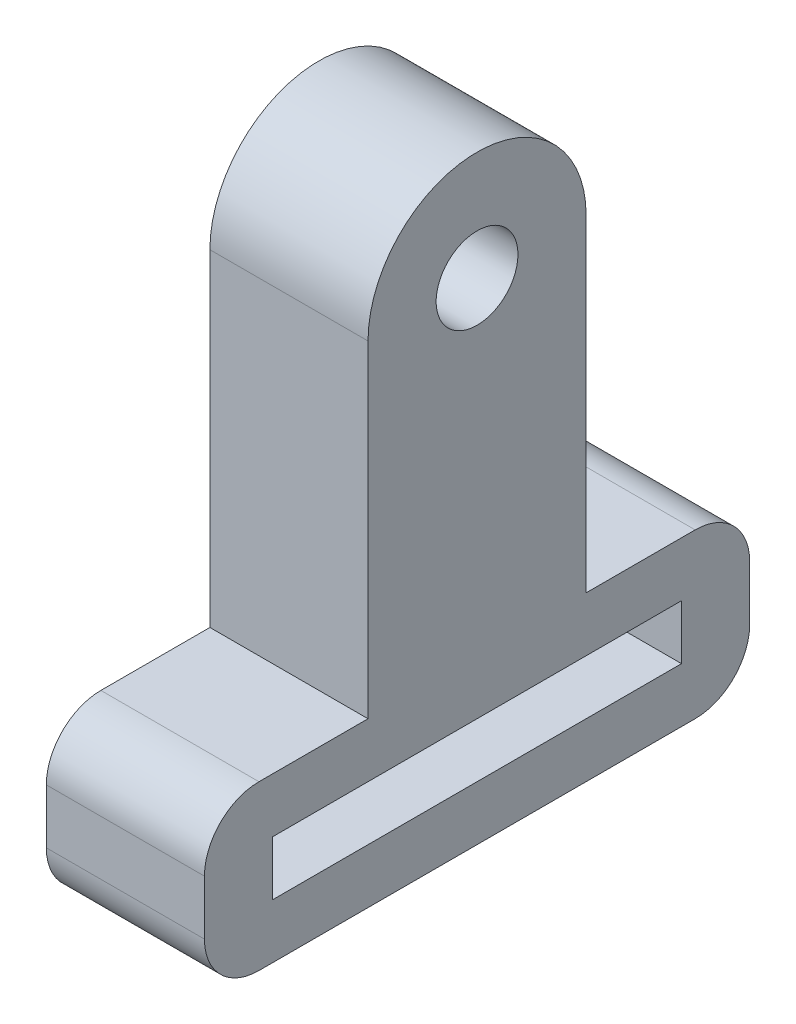
SolidWorks part; units mm, degrees
ref_plane "Alzado" through (0, 0, 0) normal (0, 0, 1) x (1, 0, 0)
ref_plane "Planta" through (0, 0, 0) normal (0, 1, 0) x (1, 0, 0)
ref_plane "Vista lateral" through (0, 0, 0) normal (1, 0, 0) x (0, 0, -1)
sketch "Croquis1" plane through (0, 0, 0) normal (1, 0, 0) x (0, 0, -1)
  line L2 (-10, 1) -> (-10, -1)
  line L3 (-8, -3) -> (8, -3)
  line L4 (10, 1) -> (10, -1)
  line L5 (-10, 3) -> (10, -3) construction
  line L6 (-10, -3) -> (10, 3) construction
  line L7 (-7.5, 1) -> (7.5, 1)
  line L8 (-7.5, 1) -> (-7.5, -1)
  line L9 (-7.5, -1) -> (7.5, -1)
  line L10 (7.5, 1) -> (7.5, -1)
  line L11 (-7.5, 1) -> (7.5, -1) construction
  line L12 (-7.5, -1) -> (7.5, 1) construction
  line L15 (-10, 3) -> (10, 3) construction
  line L27 (-4, 3) -> (-8, 3)
  line L28 (4, 3) -> (8, 3)
  line L35 (0, 3) -> (0, 15) construction
  line L36 (-4, 15) -> (-4, 3)
  line L39 (4, 15) -> (4, 3)
  circle A1 centre (0, 15) radius 1.5
  arc A2 (4, 15) -> (-4, 15) centre (0, 15) ccw
  arc A3 (8, -3) -> (10, -1) centre (8, -1) ccw
  arc A4 (8, 3) -> (10, 1) centre (8, 1) cw
  arc A5 (-10, -1) -> (-8, -3) centre (-8, -1) ccw
  arc A6 (-8, 3) -> (-10, 1) centre (-8, 1) ccw
  point P0 (0, 0)
  point P6 (0, 0)
  dimension "D18" = 8
  dimension "D17" = 3
  dimension "D6" = 2
  dimension "D2" = 20
  dimension "D3" = 2
  dimension "D4" = 15
  dimension "D5" = 6
  dimension "D16" = 12
  dimension "D23" = 2
extrude "Saliente-Extruir1" add sketch "Croquis1" along normal mid plane 5.8
